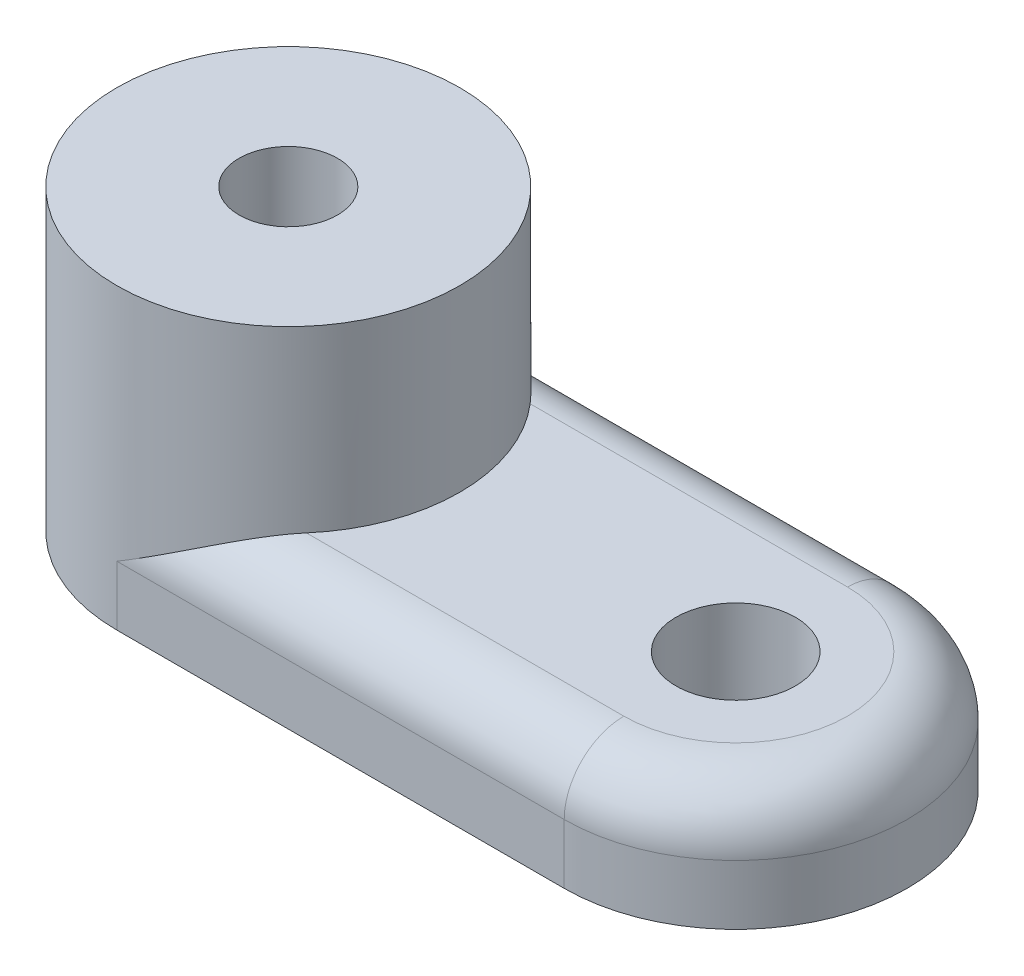
SolidWorks part; units mm, degrees
ref_plane "Front Plane" through (0, 0, 0) normal (0, 0, 1) x (1, 0, 0)
ref_plane "Top Plane" through (0, 0, 0) normal (0, 1, 0) x (1, 0, 0)
ref_plane "Right Plane" through (0, 0, 0) normal (1, 0, 0) x (0, 0, -1)
sketch "Sketch1" plane through (0, 0, 0) normal (0, 1, 0) x (1, 0, 0)
  circle A0 centre (0, 0) radius 1.65
  circle A1 centre (0, 0) radius 5.75
  dimension "D1" = 3.3
  dimension "D2" = 11.5
extrude "Boss-Extrude1" add sketch "Sketch1" along normal blind 10
sketch "Sketch2" plane through (0, 0, 0) normal (0, -1, 0) x (1, 0, 0)
  line L0 (15, 5.75) -> (0, 5.75)
  line L1 (0, 5.75) -> (5.75, 0)
  line L2 (5.75, 0) -> (0, -5.75)
  line L3 (0, -5.75) -> (15, -5.75)
  line L4 (15, -5.75) -> (9.25, 0)
  line L5 (9.25, 0) -> (15, 5.75)
  circle A0 centre (15, 0) radius 2
  circle A1 centre (15, 0) radius 5.75
  circle A2 centre (0, 0) radius 5.75 construction
  circle M1 centre (0, 0) radius 5.75
  dimension "D1" = 4
  dimension "D3" = 11.5
  dimension "D2" = 15
extrude "Boss-Extrude2" add sketch "Sketch2" against normal blind 4 contours L4 A1 L5 A0 | L5 A1 | A1 L0 L3 M1 | L4 A1 region at (7.5, 0, 0) region at (18.9509, 0, 3.9509) region at (11.6421, 0, 3.3579) region at (11.6421, 0, -3.3579)
fillet "Fillet1" radius 2 3 edges at (7.5, 4, -5.75) (20.75, 4, 0) (7.5, 4, 5.75)
